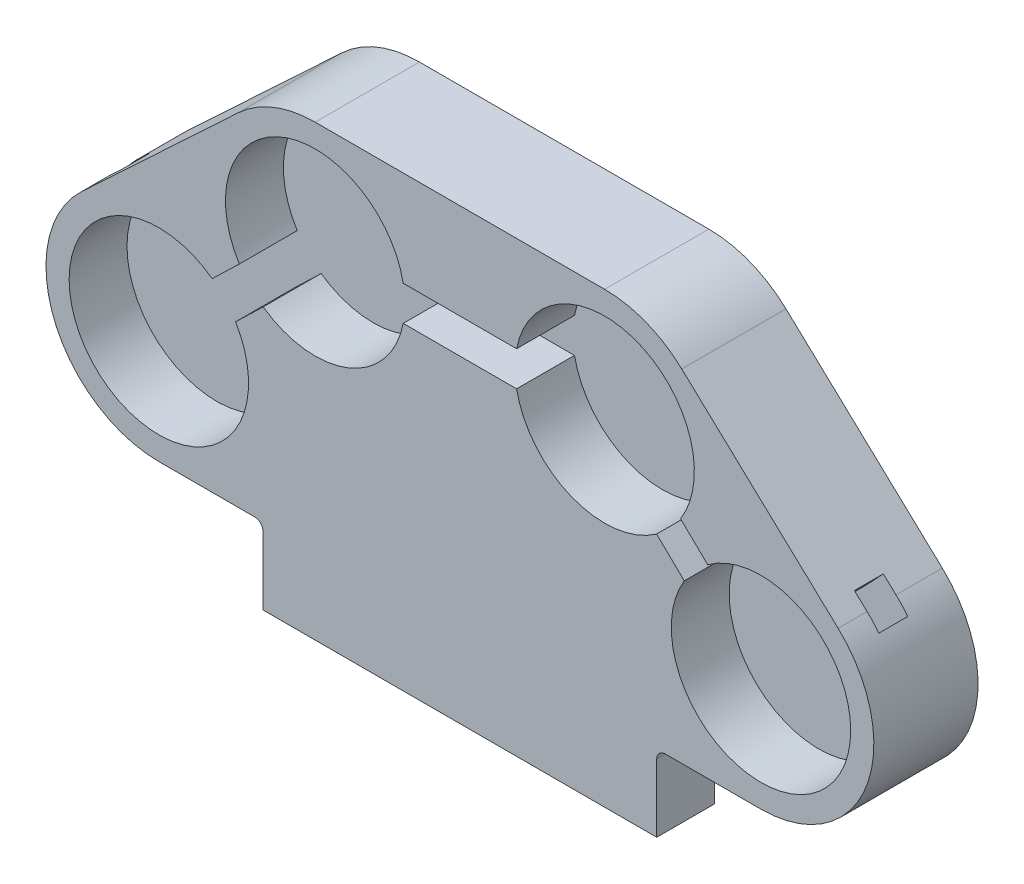
SolidWorks part; units mm, degrees
ref_plane "Front Plane" through (0, 0, 0) normal (0, 0, 1) x (1, 0, 0)
ref_plane "Top Plane" through (0, 0, 0) normal (0, 1, 0) x (1, 0, 0)
ref_plane "Right Plane" through (0, 0, 0) normal (1, 0, 0) x (0, 0, -1)
sketch "Sketch1" plane through (0, 0, 0) normal (0, 0, 1) x (1, 0, 0)
  line L0 (-11.9595, 12.7758) -> (-50.7466, -23.5332) construction
  line L1 (11.9595, 12.7758) -> (50.7466, -23.5332) construction
  line L2 (-11.9595, 12.7758) -> (11.9595, 12.7758) construction
  line L3 (-50.7466, -23.5332) -> (50.7466, -23.5332) construction
  line L4 (-17.5, -2) -> (17.5, -2) construction
  line L5 (0, 0) -> (0, -2) construction
  line L6 (-17.5, -2) -> (-17.5, 4) construction
  line L7 (-17.5, 4) -> (-20.5, 4) construction
  line L8 (-20.5, 4) -> (-20.5, -5) construction
  line L9 (-20.5, -5) -> (20.5, -5) construction
  line L10 (20.5, -5) -> (20.5, 4) construction
  line L11 (20.5, 4) -> (17.5, 4) construction
  line L12 (17.5, 4) -> (17.5, -2) construction
  line L13 (0, -2) -> (0, 40.1846) construction
  line L14 (-26.0058, 14.352) -> (-12.5, 26.995) construction
  line L15 (-32.669, 21.47) -> (-19.1632, 34.1129)
  line L16 (-26.0058, 4.602) -> (-17.75, 4.602)
  line L17 (-17, 3.852) -> (-17, -2)
  line L18 (-17, -2) -> (0, -2)
  line L19 (-12.5, 36.745) -> (0, 36.745)
  line L20 (0, 36.745) -> (0, -2)
  circle A0 centre (0, 0) radius 17.5 construction
  circle A1 centre (-26.0058, 14.352) radius 7.75
  circle A2 centre (-12.5, 26.995) radius 7.75
  circle A3 centre (-12.5, 26.995) radius 9.75 construction
  circle A4 centre (-26.0058, 14.352) radius 9.75 construction
  arc A5 (-17.75, 4.602) -> (-17, 3.852) centre (-17.75, 3.852) cw
  arc A6 (-19.1632, 34.1129) -> (-12.5, 36.745) centre (-12.5, 26.995) cw
  arc A7 (-26.0058, 4.602) -> (-32.669, 21.47) centre (-26.0058, 14.352) cw
  dimension "D1" = 35
  dimension "D8" = 15.5
  dimension "D10" = 3
  dimension "D11" = 2
  dimension "D13" = 0.75
  dimension "D2" = 93.78
  dimension "D3" = 35
  dimension "2" = 2
  dimension "D4" = 6
  dimension "D5" = 3
  dimension "D6" = 3
  dimension "D7" = 3
  dimension "D9" = 25
  dimension "D12" = 0.5
extrude "Boss-Extrude1" add sketch "Sketch1" along normal blind 5 contours A7 L16 A5 L17 L18 L20 L19 A6 L15 A2 A1 region at (-12.1141, 15.2891, 0)
mirror "Mirror1" about plane through (0, 0, 0) normal (1, 0, 0) of "Boss-Extrude1"
sketch "Sketch3" plane through (0, 0, 0) normal (0, 0, -1) x (-1, 0, 0)
  line L0 (32.669, 21.47) -> (19.1632, 34.1129) construction
  line L1 (32.669, 21.47) -> (19.1632, 34.1129)
  line L2 (12.5, 36.745) -> (-12.5, 36.745) construction
  line L3 (12.5, 36.745) -> (-12.5, 36.745)
  line L4 (-32.669, 21.47) -> (-19.1632, 34.1129) construction
  line L5 (-32.669, 21.47) -> (-19.1632, 34.1129)
  line L6 (-19.3426, 7.2341) -> (-5.8368, 19.877)
  line L7 (19.3426, 7.2341) -> (5.8368, 19.877)
  arc A0 (26.0058, 4.602) -> (32.669, 21.47) centre (26.0058, 14.352) ccw construction
  arc A1 (26.0058, 4.602) -> (32.669, 21.47) centre (26.0058, 14.352) ccw construction
  arc A2 (19.1632, 34.1129) -> (12.5, 36.745) centre (12.5, 26.995) ccw construction
  arc A3 (19.1632, 34.1129) -> (12.5, 36.745) centre (12.5, 26.995) ccw
  arc A4 (-12.5, 36.745) -> (-19.1632, 34.1129) centre (-12.5, 26.995) ccw construction
  arc A5 (-12.5, 36.745) -> (-19.1632, 34.1129) centre (-12.5, 26.995) ccw
  arc A6 (-32.669, 21.47) -> (-26.0058, 4.602) centre (-26.0058, 14.352) ccw construction
  arc A7 (-32.669, 21.47) -> (-26.0058, 4.602) centre (-26.0058, 14.352) ccw construction
  circle A8 centre (-26.0058, 14.352) radius 9.75 construction
  circle A9 centre (-12.5, 26.995) radius 9.75 construction
  circle A10 centre (12.5, 26.995) radius 9.75 construction
  circle A11 centre (26.0058, 14.352) radius 9.75 construction
  circle A12 centre (0, 13.6418) radius 8.5409 construction
  arc A13 (-5.8368, 19.877) -> (5.8368, 19.877) centre (0, 13.6418) cw
  arc A14 (-32.669, 21.47) -> (-19.3426, 7.2341) centre (-26.0058, 14.352) ccw
  arc A15 (32.669, 21.47) -> (19.3426, 7.2341) centre (26.0058, 14.352) cw
  arc M9 (26.0058, 4.602) -> (32.669, 21.47) centre (26.0058, 14.352) ccw
  line M10 (32.669, 21.47) -> (19.1632, 34.1129)
  arc M11 (19.1632, 34.1129) -> (12.5, 36.745) centre (12.5, 26.995) ccw
  line M12 (12.5, 36.745) -> (-12.5, 36.745)
  arc M13 (-12.5, 36.745) -> (-19.1632, 34.1129) centre (-12.5, 26.995) ccw
  line M14 (-19.1632, 34.1129) -> (-32.669, 21.47)
  arc M15 (-32.669, 21.47) -> (-26.0058, 4.602) centre (-26.0058, 14.352) ccw
  circle M23 centre (12.5, 26.995) radius 7.75
  circle M24 centre (26.0058, 14.352) radius 7.75
  circle M25 centre (-12.5, 26.995) radius 7.75
  circle M26 centre (-26.0058, 14.352) radius 7.75
extrude "Boss-Extrude2" add sketch "Sketch3" along normal blind 4 contours A15 A14 L6 A13 L7 M9 M10 M11 M12 M13 M14 M15 M23 M25 M26 M24 | M26 | M25 | M23 | M24 region at (0, 22.5292, 0) region at (-12.5, 26.995, 0) region at (-26.0058, 14.352, 0) region at (12.5, 26.995, 0) region at (26.0058, 14.352, 0)
sketch "Sketch4" plane through (0, 0, 0) normal (0, 0, 1) x (1, 0, 0)
  circle A0 centre (26.0058, 14.352) radius 7.75 construction
  circle A1 centre (12.5, 26.995) radius 7.75 construction
  circle A2 centre (-12.5, 26.995) radius 7.75 construction
  circle A3 centre (-26.0058, 14.352) radius 7.75 construction
  circle A4 centre (26.0058, 14.352) radius 7.75
  circle A5 centre (12.5, 26.995) radius 7.75
  circle A6 centre (-12.5, 26.995) radius 7.75
  circle A7 centre (-26.0058, 14.352) radius 7.75
extrude "Cut-Extrude1" [suppressed] cut sketch "Sketch4" against normal blind 1
sketch "Sketch5" plane through (0, 0, 5) normal (0, 0, 1) x (1, 0, 0)
  line L0 (-26.0058, 14.352) -> (-12.5, 26.995) construction
  line L1 (-17.1499, 24.6966) -> (-23.3682, 18.6909)
  line L2 (-23.3682, 18.6909) -> (-21.284, 16.533)
  line L3 (-21.284, 16.533) -> (-15.0658, 22.5387)
  line L4 (-15.0658, 22.5387) -> (-17.1499, 24.6966)
  line L5 (0, 0) -> (0, 28.253) construction
  line L6 (-12.5, 26.995) -> (12.5, 26.995) construction
  line L7 (-6.9065, 28.495) -> (8.5226, 28.495)
  line L8 (8.5226, 28.495) -> (8.5226, 25.495)
  line L9 (8.5226, 25.495) -> (-6.9065, 25.495)
  line L10 (-6.9065, 25.495) -> (-6.9065, 28.495)
  line L11 (21.284, 16.533) -> (15.0658, 22.5387)
  line L12 (23.3682, 18.6909) -> (21.284, 16.533)
  line L13 (17.1499, 24.6966) -> (23.3682, 18.6909)
  line L14 (15.0658, 22.5387) -> (17.1499, 24.6966)
  point P6 (-16.1078, 23.6176)
  point P16 (-6.9065, 26.995)
  dimension "D1" = 3
  dimension "D2" = 3
extrude "Cut-Extrude2" cut sketch "Sketch5" against normal up to surface (5 mm away) up to face at (-18.2558, 14.352, 0)
sketch "Sketch6" [suppressed] plane through (-25.9692, 27.7416, 0) normal (-0.6834, 0.73, 0) x (0.73, 0.6834, 0)
  line L0 (-16.9271, 1) -> (-1.556, 1) construction
  line L1 (-16.9271, 1) -> (-1.556, 1) construction
  line L2 (-9.1771, -5) -> (-9.1771, 4) construction
  line L3 (-7.6771, 1) -> (-10.6771, 1)
  line L4 (-7.6771, 1) -> (-7.6771, -1.5)
  line L5 (-7.6771, -1.5) -> (-10.6771, -1.5)
  line L6 (-10.6771, 1) -> (-10.6771, -1.5)
  point P8 (-9.1771, 1)
  dimension "D1" = 2.5
  dimension "D2" = 3
extrude "Cut-Extrude3" [suppressed] cut sketch "Sketch6" against normal blind 11
mirror "Mirror2" [suppressed] about plane through (0, 0, 0) normal (1, 0, 0)
sketch "Sketch7" plane through (-25.9692, 27.7416, 0) normal (-0.6834, 0.73, 0) x (0.73, 0.6834, 0)
  line L0 (-16.9271, 0) -> (-1.556, 0) construction
  line L1 (-7.6771, 0) -> (-10.6771, 0)
  line L2 (-7.6771, 0) -> (-7.6771, -2.5)
  line L3 (-7.6771, -2.5) -> (-10.6771, -2.5)
  line L4 (-10.6771, 0) -> (-10.6771, -2.5)
  line L5 (-16.9271, 0) -> (-1.556, 0) construction
  line L8 (-9.1771, -5) -> (-9.1771, 4) construction
  point P6 (-7.4615, 0)
  point P9 (-9.1771, -2.5)
  dimension "D1" = 3
  dimension "D2" = 2.5
extrude "Cut-Extrude4" cut sketch "Sketch7" against normal blind 10
mirror "Mirror3" about plane through (0, 0, 0) normal (1, 0, 0) of "Cut-Extrude4"
